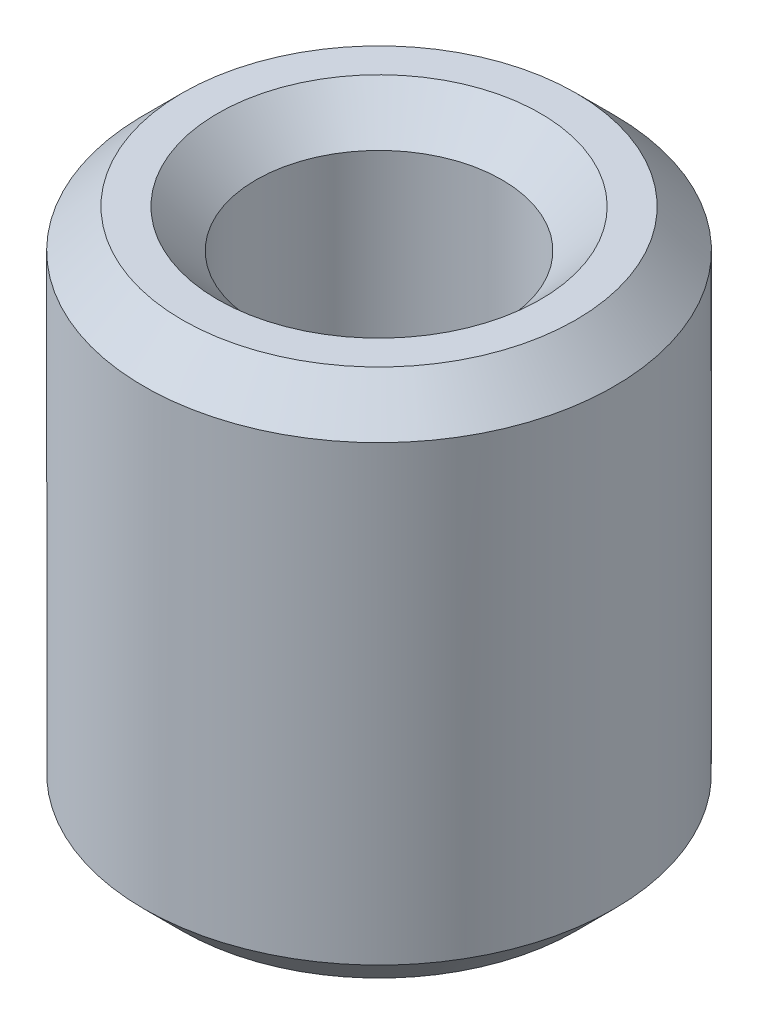
SolidWorks part; units mm, degrees
ref_plane "Front Plane" through (0, 0, 0) normal (0, 0, 1) x (1, 0, 0)
ref_plane "Top Plane" through (0, 0, 0) normal (0, 1, 0) x (1, 0, 0)
ref_plane "Right Plane" through (0, 0, 0) normal (1, 0, 0) x (0, 0, -1)
sketch "Sketch1" plane through (0, 0, 0) normal (0, 1, 0) x (1, 0, 0)
  circle A0 centre (0, 0) radius 22.5
  dimension "SLEEVE_OD" = 45
extrude "Boss-Extrude1" add sketch "Sketch1" along normal blind 50.659
sketch "Sketch2" plane through (0, 0, 0) normal (0, 1, 0) x (1, 0, 0)
  circle A0 centre (0, 0) radius 11.7689
  dimension "BORE_D" = 23.5378
extrude "Cut-Extrude1" cut sketch "Sketch2" along normal through all
chamfer "Chamfer1" distance 3.6739 angle 45 4 edges at (0, 50.659, 11.7689) (0, 0, 11.7689) (0, 0, 22.5) (0, 50.659, 22.5)
